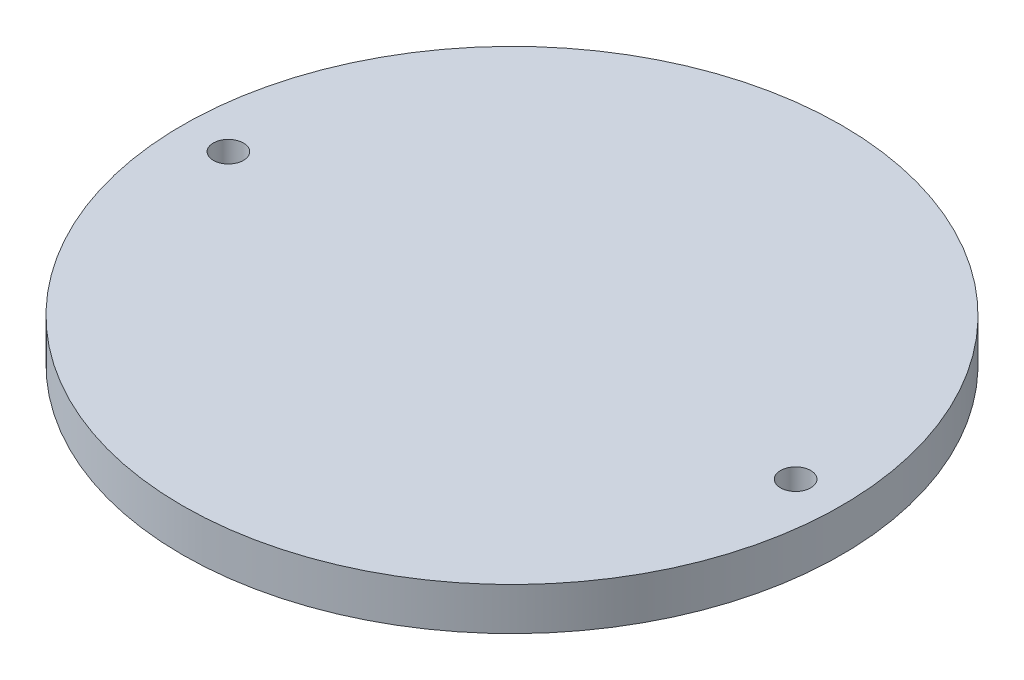
SolidWorks part; units mm, degrees
ref_plane "Front Plane" through (0, 0, 0) normal (0, 0, 1) x (1, 0, 0)
ref_plane "Top Plane" through (0, 0, 0) normal (0, 1, 0) x (1, 0, 0)
ref_plane "Right Plane" through (0, 0, 0) normal (1, 0, 0) x (0, 0, -1)
sketch "Payload Cover Profile" plane through (0, 0, 0) normal (0, 1, 0) x (1, 0, 0)
  circle A0 centre (0, 0) radius 73.787
  dimension "D1" = 147.574
extrude "Payload Cover Body" add sketch "Payload Cover Profile" along normal blind 9.525 contours A0
sketch "Threaded Rod Hole Profiles" plane through (0, 9.525, 0) normal (0, 1, 0) x (1, 0, 0)
  line L0 (-63.5, 0) -> (63.5, 0) construction
  circle A0 centre (-63.5, 0) radius 3.3782
  circle A1 centre (63.5, 0) radius 3.3782
  point P4 (0, 0)
  dimension "D1" = 6.7564
  dimension "D2" = 63.5
extrude "Threaded Rod Hole Cuts" cut sketch "Threaded Rod Hole Profiles" against normal through all
